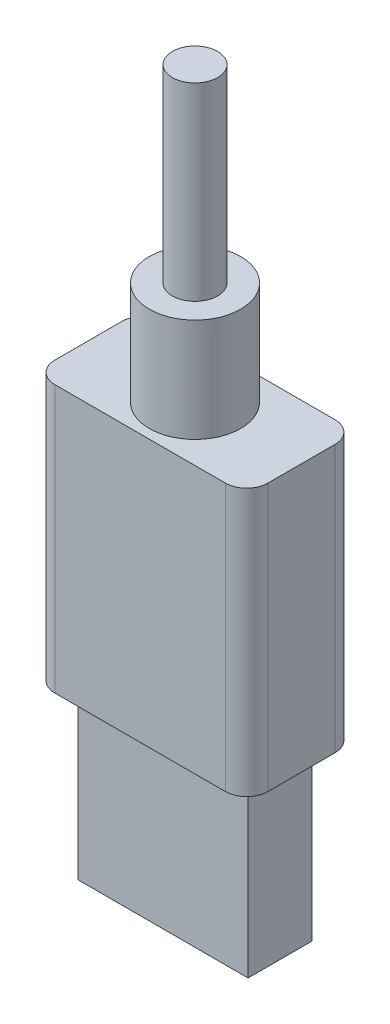
SolidWorks part; units mm, degrees
ref_plane "Front Plane" through (0, 0, 0) normal (0, 0, 1) x (1, 0, 0)
ref_plane "Top Plane" through (0, 0, 0) normal (0, 1, 0) x (1, 0, 0)
ref_plane "Right Plane" through (0, 0, 0) normal (1, 0, 0) x (0, 0, -1)
sketch "Sketch1" plane through (0, 0, 0) normal (0, 1, 0) x (1, 0, 0)
  line L1 (-6, -2.25) -> (6, -2.25)
  line L2 (-6, -2.25) -> (-6, 2.25)
  line L3 (-6, 2.25) -> (6, 2.25)
  line L4 (6, -2.25) -> (6, 2.25)
  line L5 (-6, -2.25) -> (6, 2.25) construction
  line L6 (-6, 2.25) -> (6, -2.25) construction
  point P0 (0, 0)
  dimension "D1" = 12
  dimension "D2" = 4.5
extrude "Boss-Extrude1" add sketch "Sketch1" along normal blind 12.23
sketch "Sketch2" plane through (0, 12.23, 0) normal (0, 1, 0) x (1, 0, 0)
  line L1 (-6.025, -3.875) -> (6.025, -3.875)
  line L2 (-7.525, -2.375) -> (-7.525, 2.375)
  line L3 (-6.025, 3.875) -> (6.025, 3.875)
  line L4 (7.525, -2.375) -> (7.525, 2.375)
  line L5 (-7.525, -3.875) -> (7.525, 3.875) construction
  line L6 (-7.525, 3.875) -> (7.525, -3.875) construction
  arc A0 (-6.025, -3.875) -> (-7.525, -2.375) centre (-6.025, -2.375) cw
  arc A1 (6.025, -3.875) -> (7.525, -2.375) centre (6.025, -2.375) ccw
  arc A2 (6.025, 3.875) -> (7.525, 2.375) centre (6.025, 2.375) cw
  arc A3 (-7.525, 2.375) -> (-6.025, 3.875) centre (-6.025, 2.375) cw
  point P0 (0, 0)
  dimension "D3" = 1.5
  dimension "D1" = 7.75
  dimension "D2" = 15.05
extrude "Boss-Extrude2" add sketch "Sketch2" along normal blind 18.87
sketch "Sketch3" plane through (0, 31.1, 0) normal (0, 1, 0) x (1, 0, 0)
  circle A0 centre (0, 0) radius 3.225
  dimension "D1" = 6.45
extrude "Boss-Extrude3" add sketch "Sketch3" along normal blind 7.3
sketch "Sketch4" plane through (0, 38.4, 0) normal (0, 1, 0) x (1, 0, 0)
  circle A0 centre (0, 0) radius 1.6
  dimension "D1" = 3.2
extrude "Boss-Extrude4" add sketch "Sketch4" along normal blind 13.36
